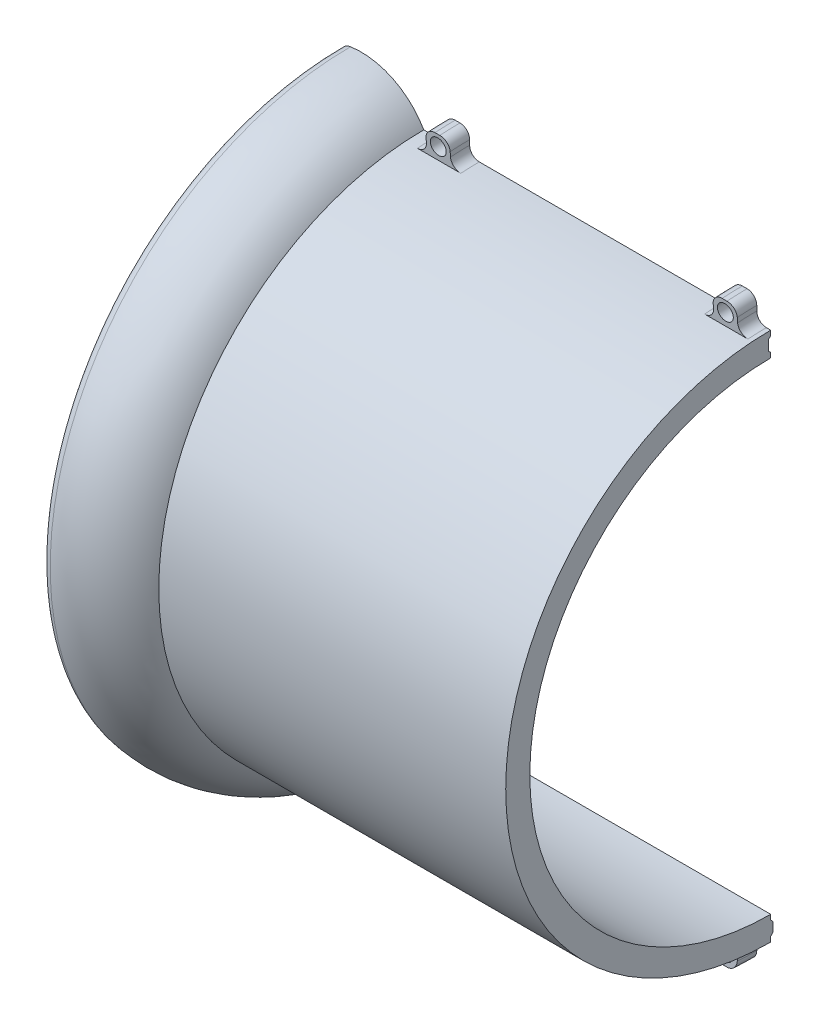
SolidWorks part; units mm, degrees
ref_plane "Front Plane" through (0, 0, 0) normal (0, 0, 1) x (1, 0, 0)
ref_plane "Top Plane" through (0, 0, 0) normal (0, 1, 0) x (1, 0, 0)
ref_plane "Right Plane" through (0, 0, 0) normal (1, 0, 0) x (0, 0, -1)
sketch "Sketch1" plane through (0, 0, 0) normal (0, 0, 1) x (1, 0, 0)
  line L0 (0, 115.2367) -> (0, -115.2367) construction
  line L1 (-156.5533, 0) -> (156.5533, 0) construction
  line L2 (4.3301, 50) -> (0, 47.5)
  line L3 (4.3301, -50) -> (0, -47.5) construction
  line L4 (4.3301, 50) -> (75, 50)
  line L6 (75, 50) -> (75, 55)
  line L7 (75, 55) -> (2.9904, 55)
  line L12 (-13.4202, 56.8969) -> (-15.1303, 61.5954)
  line L13 (-13.4202, 56.8969) -> (-10, 47.5) construction
  line L14 (-10, 47.5) -> (-18.6603, 47.5) construction
  arc A0 (0, 47.5) -> (-13.4202, 56.8969) centre (-10, 47.5) ccw
  arc A2 (2.9904, 55) -> (-15.1303, 61.5954) centre (-10, 47.5) ccw
  point P4 (0, 0)
  point P6 (0, 47.5)
  point P8 (0, 0)
  point P9 (4.3301, 50)
  dimension "D8" = 30
  dimension "D7" = 10
  dimension "D5" = 70
  dimension "D1" = 47.5
  dimension "D2" = 50
  dimension "D3" = 60
  dimension "D4" = 75
  dimension "D6" = 5
revolve "Revolve1" add sketch "Sketch1" angle 180 about L1
fillet "Fillet1" radius 2.5 1 edges at (4.3301, 0, 50)
fillet "Fillet2" radius 2.5 2 edges at (-15.1303, 0, 61.5954) (-13.4202, 0, 56.8969)
sketch "Sketch3" plane through (75, 0, 0) normal (1, 0, 0) x (0, 0, -1)
  line L0 (0, 49.1368) -> (0, -49.1368) construction
  line L1 (0, 54) -> (0, 51)
  line L2 (0, 51) -> (-0.5, 51.5)
  line L3 (-0.5, 51.5) -> (-0.5, 53.5)
  line L4 (-0.5, 53.5) -> (0, 54)
  line L5 (0, 50) -> (0, 55) construction
  point P5 (0, 52.5)
  point P10 (0, 52.5)
  dimension "D1" = 2
  dimension "D2" = 3
  dimension "D3" = 45
  dimension "D4" = 0
extrude "Cut-Extrude1" cut sketch "Sketch3" against normal blind 70
sketch "Sketch5" plane through (75, 0, 0) normal (1, 0, 0) x (0, 0, -1)
  line L0 (0, -51.05) -> (0, -53.95)
  line L1 (0, 49.1368) -> (0, -49.1368) construction
  line L2 (0, -53.95) -> (0.5, -53.45)
  line L3 (0.5, -53.45) -> (0.5, -51.55)
  line L4 (0.5, -51.55) -> (0, -51.05)
  line L5 (0, -50) -> (0, -55) construction
  point P5 (0, -52.5)
  point P10 (0, -52.5)
  dimension "D1" = 1.9
  dimension "D2" = 2.9
  dimension "D3" = 45
  dimension "D4" = 0
extrude "Boss-Extrude1" add sketch "Sketch5" against normal blind 70
sketch "Sketch7" plane through (0, 0, 0) normal (0, 0, -1) x (-1, 0, 0)
  line L0 (-72.1086, 55) -> (-67.1086, 55)
  line L1 (-75, 55) -> (-2.9904, 55) construction
  line L2 (-67.1086, 55) -> (-67.1086, 60)
  line L3 (-67.1086, 60) -> (-72.1086, 60)
  line L4 (-72.1086, 60) -> (-72.1086, 55)
  line L5 (-7.5157, 55) -> (-7.5157, 60)
  line L6 (-7.5157, 60) -> (-12.5157, 60)
  line L7 (-12.5157, 60) -> (-12.5157, 55)
  line L8 (-12.5157, 55) -> (-7.5157, 55)
  dimension "D1" = 5
  dimension "D2" = 5
ref_axis "Axis1" through (75, 0, 0) along (-1, 0, 0)
revolve "Revolve2" add sketch "Sketch7" angle 4 about axis through (75, 0, 0) along (-1, 0, 0) reverse direction yes
hole_wizard "Ø3.0mm Dowel Hole2" positions "Sketch10" profile "Sketch11" hole size "Ø3.0" standard "ANSI Metric"
sketch "Sketch10" plane through (0, 0, 0) normal (0, 0, -1) x (-1, 0, 0)
  line L0 (-67.1086, 60) -> (-72.1086, 60) construction
  line L1 (-72.1086, 60) -> (-72.1086, 55) construction
  line L2 (-12.5157, 60) -> (-12.5157, 55) construction
  line L4 (-7.5157, 60) -> (-12.5157, 60) construction
  point P0 (-69.6086, 57.5)
  point P2 (-10.0157, 57.5)
  point P15 (-8.4719, 60)
  dimension "D1" = 2.5
  dimension "D2" = 2.5
  dimension "D3" = 2.5
  dimension "D4" = 2.5
sketch "Sketch11" plane through (69.6086, 57.5, 0) normal (1, 0, 0) x (0, 1, 0)
  line L0 (0, 0) -> (0, 45.9914)
  line L1 (0, 45.9914) -> (1.65, 45)
  line L2 (1.65, 45) -> (1.65, 0)
  line L5 (1.65, 0) -> (0, 0)
  line L10 (0, 45.9914) -> (-1.65, 45) construction
  line L11 (0, -6.35) -> (0, 107.95) construction
  dimension "Hole Dia." = 3.3
  dimension "Hole Depth" = 45
  dimension "Drill Angle" = 118
fillet "Fillet3" radius 2 8 edges at (67.1086, 59.9634, 2.094) (72.1086, 59.9634, 2.094) (7.5157, 59.9634, 2.094) (12.5157, 59.9634, 2.094) (67.1086, 54.9665, 1.9195) (72.1086, 54.9665, 1.9195) (12.5157, 54.9665, 1.9195) (7.5157, 54.9665, 1.9195)
mirror "Mirror3" about plane through (0, 0, 0) normal (0, 1, 0) of "Fillet3", "Ø3.0mm Dowel Hole2", "Revolve2"
